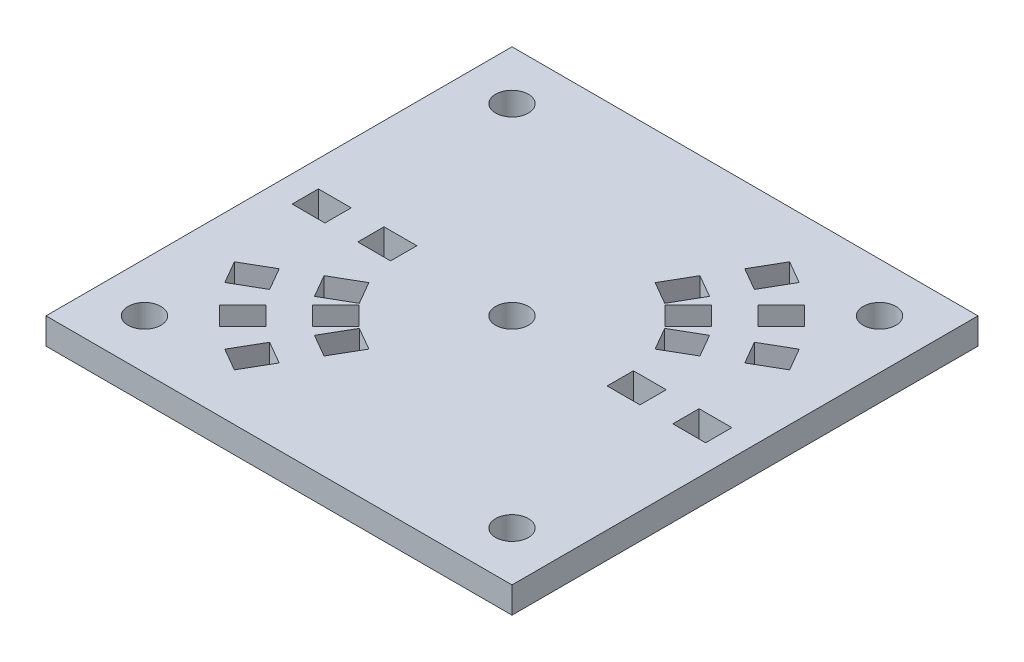
SolidWorks part; units mm, degrees
ref_plane "Front Plane" through (0, 0, 0) normal (0, 0, 1) x (1, 0, 0)
ref_plane "Top Plane" through (0, 0, 0) normal (0, 1, 0) x (1, 0, 0)
ref_plane "Right Plane" through (0, 0, 0) normal (1, 0, 0) x (0, 0, -1)
sketch "Sketch1" plane through (0, 0, 0) normal (0, 1, 0) x (1, 0, 0)
  line L0 (-1.4151, 22.54) -> (-1.4151, -67.6199) construction
  line L1 (-46.495, 22.54) -> (43.6649, 22.54)
  line L2 (-46.495, 22.54) -> (-46.495, -67.6199)
  line L3 (-46.495, -67.6199) -> (43.6649, -67.6199)
  line L4 (43.6649, 22.54) -> (43.6649, -67.6199)
  line L5 (-46.495, -22.54) -> (43.6649, -22.54) construction
  line L6 (-39.3946, -9.7338) -> (-33.261, -11.3773) [skipped]
  line L7 (-41.415, -20) -> (-35.065, -20)
  line L8 (-41.415, -20) -> (-41.415, -25.08)
  line L9 (-41.415, -25.08) -> (-35.065, -25.08)
  line L10 (-35.065, -20) -> (-35.065, -25.08)
  line L11 (-28.715, -20) -> (-22.365, -20)
  line L12 (-28.715, -20) -> (-28.715, -25.08)
  line L13 (-28.715, -25.08) -> (-22.365, -25.08)
  line L14 (-22.365, -20) -> (-22.365, -25.08)
  line L19 (-39.3946, -9.7338) -> (-40.7094, -14.6407) [skipped]
  line L20 (-40.7094, -14.6407) -> (-34.5758, -16.2842) [skipped]
  line L21 (-33.261, -11.3773) -> (-34.5758, -16.2842) [skipped]
  line L22 (-27.1274, -13.0208) -> (-20.9937, -14.6643) [skipped]
  line L23 (-27.1274, -13.0208) -> (-28.4422, -17.9277) [skipped]
  line L24 (-28.4422, -17.9277) -> (-22.3085, -19.5712) [skipped]
  line L25 (-20.9937, -14.6643) -> (-22.3085, -19.5712) [skipped]
  line L30 (-34.786, -0.3403) -> (-29.2868, -3.5153) [skipped]
  line L31 (-34.786, -0.3403) -> (-37.326, -4.7397) [skipped]
  line L32 (-37.326, -4.7397) -> (-31.8268, -7.9147) [skipped]
  line L33 (-29.2868, -3.5153) -> (-31.8268, -7.9147) [skipped]
  line L34 (-23.7875, -6.6903) -> (-18.2882, -9.8653) [skipped]
  line L35 (-23.7875, -6.6903) -> (-26.3275, -11.0897) [skipped]
  line L36 (-26.3275, -11.0897) -> (-20.8282, -14.2647) [skipped]
  line L37 (-18.2882, -9.8653) -> (-20.8282, -14.2647) [skipped]
  line L42 (-27.9032, 7.5403) -> (-23.4131, 3.0502) [skipped]
  line L43 (-27.9032, 7.5403) -> (-31.4953, 3.9482) [skipped]
  line L44 (-31.4953, 3.9482) -> (-27.0052, -0.5419) [skipped]
  line L45 (-23.4131, 3.0502) -> (-27.0052, -0.5419) [skipped]
  line L46 (-18.923, -1.44) -> (-14.4328, -5.9301) [skipped]
  line L47 (-18.923, -1.44) -> (-22.5151, -5.0321) [skipped]
  line L48 (-22.5151, -5.0321) -> (-18.0249, -9.5222) [skipped]
  line L49 (-14.4328, -5.9301) -> (-18.0249, -9.5222) [skipped]
  line L54 (-19.2153, 13.371) -> (-16.0403, 7.8717) [skipped]
  line L55 (-19.2153, 13.371) -> (-23.6147, 10.831) [skipped]
  line L56 (-23.6147, 10.831) -> (-20.4397, 5.3317) [skipped]
  line L57 (-16.0403, 7.8717) -> (-20.4397, 5.3317) [skipped]
  line L58 (-12.8653, 2.3725) -> (-9.6903, -3.1268) [skipped]
  line L59 (-12.8653, 2.3725) -> (-17.2647, -0.1675) [skipped]
  line L60 (-17.2647, -0.1675) -> (-14.0897, -5.6668) [skipped]
  line L61 (-9.6903, -3.1268) -> (-14.0897, -5.6668) [skipped]
  line L66 (-9.3144, 16.7544) -> (-7.6709, 10.6208) [skipped]
  line L67 (-9.3144, 16.7544) -> (-14.2213, 15.4396) [skipped]
  line L68 (-14.2213, 15.4396) -> (-12.5778, 9.306) [skipped]
  line L69 (-7.6709, 10.6208) -> (-12.5778, 9.306) [skipped]
  line L70 (-6.0274, 4.4871) -> (-4.3839, -1.6465) [skipped]
  line L71 (-6.0274, 4.4871) -> (-10.9343, 3.1723) [skipped]
  line L72 (-10.9343, 3.1723) -> (-9.2908, -2.9613) [skipped]
  line L73 (-4.3839, -1.6465) -> (-9.2908, -2.9613) [skipped]
  line L78 (1.1249, 17.46) -> (1.1249, 11.11) [skipped]
  line L79 (1.1249, 17.46) -> (-3.9551, 17.46) [skipped]
  line L80 (-3.9551, 17.46) -> (-3.9551, 11.11) [skipped]
  line L81 (1.1249, 11.11) -> (-3.9551, 11.11) [skipped]
  line L82 (1.1249, 4.76) -> (1.1249, -1.59) [skipped]
  line L83 (1.1249, 4.76) -> (-3.9551, 4.76) [skipped]
  line L84 (-3.9551, 4.76) -> (-3.9551, -1.59) [skipped]
  line L85 (1.1249, -1.59) -> (-3.9551, -1.59) [skipped]
  line L90 (11.3911, 15.4396) -> (9.7476, 9.306) [skipped]
  line L91 (11.3911, 15.4396) -> (6.4842, 16.7544) [skipped]
  line L92 (6.4842, 16.7544) -> (4.8407, 10.6208) [skipped]
  line L93 (9.7476, 9.306) -> (4.8407, 10.6208) [skipped]
  line L94 (8.1041, 3.1723) -> (6.4606, -2.9613) [skipped]
  line L95 (8.1041, 3.1723) -> (3.1972, 4.4871) [skipped]
  line L96 (3.1972, 4.4871) -> (1.5537, -1.6465) [skipped]
  line L97 (6.4606, -2.9613) -> (1.5537, -1.6465) [skipped]
  line L102 (20.7846, 10.831) -> (17.6096, 5.3317)
  line L103 (20.7846, 10.831) -> (16.3852, 13.371)
  line L104 (16.3852, 13.371) -> (13.2102, 7.8717)
  line L105 (17.6096, 5.3317) -> (13.2102, 7.8717)
  line L106 (14.4346, -0.1675) -> (11.2596, -5.6668)
  line L107 (14.4346, -0.1675) -> (10.0352, 2.3725)
  line L108 (10.0352, 2.3725) -> (6.8602, -3.1268)
  line L109 (11.2596, -5.6668) -> (6.8602, -3.1268)
  line L114 (28.6652, 3.9482) -> (24.1751, -0.5419)
  line L115 (28.6652, 3.9482) -> (25.0731, 7.5403)
  line L116 (25.0731, 7.5403) -> (20.583, 3.0502)
  line L117 (24.1751, -0.5419) -> (20.583, 3.0502)
  line L118 (19.6849, -5.0321) -> (15.1948, -9.5222)
  line L119 (19.6849, -5.0321) -> (16.0928, -1.44)
  line L120 (16.0928, -1.44) -> (11.6027, -5.9301)
  line L121 (15.1948, -9.5222) -> (11.6027, -5.9301)
  line L126 (34.4959, -4.7397) -> (28.9966, -7.9147)
  line L127 (34.4959, -4.7397) -> (31.9559, -0.3403)
  line L128 (31.9559, -0.3403) -> (26.4566, -3.5153)
  line L129 (28.9966, -7.9147) -> (26.4566, -3.5153)
  line L130 (23.4974, -11.0897) -> (17.9981, -14.2647)
  line L131 (23.4974, -11.0897) -> (20.9574, -6.6903)
  line L132 (20.9574, -6.6903) -> (15.4581, -9.8653)
  line L133 (17.9981, -14.2647) -> (15.4581, -9.8653)
  line L138 (37.8793, -14.6407) -> (31.7457, -16.2842) [skipped]
  line L139 (37.8793, -14.6407) -> (36.5645, -9.7338) [skipped]
  line L140 (36.5645, -9.7338) -> (30.4309, -11.3773) [skipped]
  line L141 (31.7457, -16.2842) -> (30.4309, -11.3773) [skipped]
  line L142 (25.612, -17.9277) -> (19.4784, -19.5712) [skipped]
  line L143 (25.612, -17.9277) -> (24.2972, -13.0208) [skipped]
  line L144 (24.2972, -13.0208) -> (18.1636, -14.6643) [skipped]
  line L145 (19.4784, -19.5712) -> (18.1636, -14.6643) [skipped]
  line L150 (38.5849, -25.08) -> (32.2349, -25.08)
  line L151 (38.5849, -25.08) -> (38.5849, -20)
  line L152 (38.5849, -20) -> (32.2349, -20)
  line L153 (32.2349, -25.08) -> (32.2349, -20)
  line L154 (25.8849, -25.08) -> (19.5349, -25.08)
  line L155 (25.8849, -25.08) -> (25.8849, -20)
  line L156 (25.8849, -20) -> (19.5349, -20)
  line L157 (19.5349, -25.08) -> (19.5349, -20)
  line L162 (36.5645, -35.3462) -> (30.4309, -33.7027) [skipped]
  line L163 (36.5645, -35.3462) -> (37.8793, -30.4392) [skipped]
  line L164 (37.8793, -30.4392) -> (31.7457, -28.7957) [skipped]
  line L165 (30.4309, -33.7027) -> (31.7457, -28.7957) [skipped]
  line L166 (24.2972, -32.0592) -> (18.1636, -30.4156) [skipped]
  line L167 (24.2972, -32.0592) -> (25.612, -27.1522) [skipped]
  line L168 (25.612, -27.1522) -> (19.4784, -25.5087) [skipped]
  line L169 (18.1636, -30.4156) -> (19.4784, -25.5087) [skipped]
  line L174 (31.9559, -44.7396) -> (26.4566, -41.5646) [skipped]
  line L175 (31.9559, -44.7396) -> (34.4959, -40.3402) [skipped]
  line L176 (34.4959, -40.3402) -> (28.9966, -37.1652) [skipped]
  line L177 (26.4566, -41.5646) -> (28.9966, -37.1652) [skipped]
  line L178 (20.9574, -38.3896) -> (15.4581, -35.2146) [skipped]
  line L179 (20.9574, -38.3896) -> (23.4974, -33.9902) [skipped]
  line L180 (23.4974, -33.9902) -> (17.9981, -30.8152) [skipped]
  line L181 (15.4581, -35.2146) -> (17.9981, -30.8152) [skipped]
  line L186 (25.0731, -52.6202) -> (20.583, -48.1301) [skipped]
  line L187 (25.0731, -52.6202) -> (28.6652, -49.0281) [skipped]
  line L188 (28.6652, -49.0281) -> (24.1751, -44.538) [skipped]
  line L189 (20.583, -48.1301) -> (24.1751, -44.538) [skipped]
  line L190 (16.0928, -43.64) -> (11.6027, -39.1498) [skipped]
  line L191 (16.0928, -43.64) -> (19.6849, -40.0479) [skipped]
  line L192 (19.6849, -40.0479) -> (15.1948, -35.5577) [skipped]
  line L193 (11.6027, -39.1498) -> (15.1948, -35.5577) [skipped]
  line L198 (16.3852, -58.4509) -> (13.2102, -52.9516) [skipped]
  line L199 (16.3852, -58.4509) -> (20.7846, -55.9109) [skipped]
  line L200 (20.7846, -55.9109) -> (17.6096, -50.4116) [skipped]
  line L201 (13.2102, -52.9516) -> (17.6096, -50.4116) [skipped]
  line L202 (10.0352, -47.4524) -> (6.8602, -41.9531) [skipped]
  line L203 (10.0352, -47.4524) -> (14.4346, -44.9124) [skipped]
  line L204 (14.4346, -44.9124) -> (11.2596, -39.4131) [skipped]
  line L205 (6.8602, -41.9531) -> (11.2596, -39.4131) [skipped]
  line L210 (6.4842, -61.8343) -> (4.8407, -55.7007) [skipped]
  line L211 (6.4842, -61.8343) -> (11.3911, -60.5195) [skipped]
  line L212 (11.3911, -60.5195) -> (9.7476, -54.3859) [skipped]
  line L213 (4.8407, -55.7007) -> (9.7476, -54.3859) [skipped]
  line L214 (3.1972, -49.5671) -> (1.5537, -43.4334) [skipped]
  line L215 (3.1972, -49.5671) -> (8.1041, -48.2523) [skipped]
  line L216 (8.1041, -48.2523) -> (6.4606, -42.1186) [skipped]
  line L217 (1.5537, -43.4334) -> (6.4606, -42.1186) [skipped]
  line L222 (-3.9551, -62.5399) -> (-3.9551, -56.1899) [skipped]
  line L223 (-3.9551, -62.5399) -> (1.1249, -62.5399) [skipped]
  line L224 (1.1249, -62.5399) -> (1.1249, -56.1899) [skipped]
  line L225 (-3.9551, -56.1899) -> (1.1249, -56.1899) [skipped]
  line L226 (-3.9551, -49.8399) -> (-3.9551, -43.4899) [skipped]
  line L227 (-3.9551, -49.8399) -> (1.1249, -49.8399) [skipped]
  line L228 (1.1249, -49.8399) -> (1.1249, -43.4899) [skipped]
  line L229 (-3.9551, -43.4899) -> (1.1249, -43.4899) [skipped]
  line L234 (-14.2213, -60.5195) -> (-12.5778, -54.3859) [skipped]
  line L235 (-14.2213, -60.5195) -> (-9.3144, -61.8343) [skipped]
  line L236 (-9.3144, -61.8343) -> (-7.6709, -55.7007) [skipped]
  line L237 (-12.5778, -54.3859) -> (-7.6709, -55.7007) [skipped]
  line L238 (-10.9343, -48.2523) -> (-9.2908, -42.1186) [skipped]
  line L239 (-10.9343, -48.2523) -> (-6.0274, -49.5671) [skipped]
  line L240 (-6.0274, -49.5671) -> (-4.3839, -43.4334) [skipped]
  line L241 (-9.2908, -42.1186) -> (-4.3839, -43.4334) [skipped]
  line L246 (-23.6147, -55.9109) -> (-20.4397, -50.4116)
  line L247 (-23.6147, -55.9109) -> (-19.2153, -58.4509)
  line L248 (-19.2153, -58.4509) -> (-16.0403, -52.9516)
  line L249 (-20.4397, -50.4116) -> (-16.0403, -52.9516)
  line L250 (-17.2647, -44.9124) -> (-14.0897, -39.4131)
  line L251 (-17.2647, -44.9124) -> (-12.8653, -47.4524)
  line L252 (-12.8653, -47.4524) -> (-9.6903, -41.9531)
  line L253 (-14.0897, -39.4131) -> (-9.6903, -41.9531)
  line L258 (-31.4953, -49.0281) -> (-27.0052, -44.538)
  line L259 (-31.4953, -49.0281) -> (-27.9032, -52.6202)
  line L260 (-27.9032, -52.6202) -> (-23.4131, -48.1301)
  line L261 (-27.0052, -44.538) -> (-23.4131, -48.1301)
  line L262 (-22.5151, -40.0479) -> (-18.0249, -35.5577)
  line L263 (-22.5151, -40.0479) -> (-18.923, -43.64)
  line L264 (-18.923, -43.64) -> (-14.4328, -39.1498)
  line L265 (-18.0249, -35.5577) -> (-14.4328, -39.1498)
  line L270 (-37.326, -40.3402) -> (-31.8268, -37.1652)
  line L271 (-37.326, -40.3402) -> (-34.786, -44.7396)
  line L272 (-34.786, -44.7396) -> (-29.2868, -41.5646)
  line L273 (-31.8268, -37.1652) -> (-29.2868, -41.5646)
  line L274 (-26.3275, -33.9902) -> (-20.8282, -30.8152)
  line L275 (-26.3275, -33.9902) -> (-23.7875, -38.3896)
  line L276 (-23.7875, -38.3896) -> (-18.2882, -35.2146)
  line L277 (-20.8282, -30.8152) -> (-18.2882, -35.2146)
  line L282 (-40.7094, -30.4392) -> (-34.5758, -28.7957) [skipped]
  line L283 (-40.7094, -30.4392) -> (-39.3946, -35.3462) [skipped]
  line L284 (-39.3946, -35.3462) -> (-33.261, -33.7027) [skipped]
  line L285 (-34.5758, -28.7957) -> (-33.261, -33.7027) [skipped]
  line L286 (-28.4422, -27.1522) -> (-22.3085, -25.5087) [skipped]
  line L287 (-28.4422, -27.1522) -> (-27.1274, -32.0592) [skipped]
  line L288 (-27.1274, -32.0592) -> (-20.9937, -30.4156) [skipped]
  line L289 (-22.3085, -25.5087) -> (-20.9937, -30.4156) [skipped]
  point P20 (-1.4151, -22.54)
  point P300 (-1.4151, -22.54)
  dimension "D1" = 90.1598
  dimension "D2" = 90.1598
  dimension "D3" = 6.35
  dimension "D4" = 6.35
  dimension "D5" = 6.35
  dimension "D8" = 5.08
  dimension "D9" = 2.54
  dimension "D10" = 5.08
  dimension "D12" = 5.08
  dimension "D14" = 2.54
  dimension "D15" = 24
extrude "Boss-Extrude1" add sketch "Sketch1" along normal blind 5.08
sketch "Sketch2" plane through (0, 5.08, 0) normal (0, 1, 0) x (1, 0, 0)
  line L0 (43.6649, 22.54) -> (-46.495, 22.54) construction
  line L1 (-46.495, 22.54) -> (-46.495, -67.6199) construction
  line L2 (43.6649, -67.6199) -> (43.6649, 22.54) construction
  line L3 (-46.495, -67.6199) -> (43.6649, -67.6199) construction
  line L4 (-1.4151, 22.54) -> (-1.4151, -67.6199) construction
  line L5 (-46.495, -22.54) -> (43.6649, -22.54) construction
  circle A0 centre (-36.97, 13.015) radius 3.175
  circle A1 centre (-36.97, -58.0949) radius 3.175
  circle A2 centre (34.1399, -58.0949) radius 3.175
  circle A3 centre (34.1399, 13.015) radius 3.175
  circle A4 centre (-1.4151, -22.54) radius 3.175
  dimension "D1" = 6.35
  dimension "D2" = 6.35
  dimension "D3" = 6.35
  dimension "D4" = 6.35
  dimension "D13" = 6.35
  dimension "D5" = 9.525
  dimension "D6" = 9.525
  dimension "D7" = 9.525
  dimension "D8" = 9.525
  dimension "D9" = 9.525
  dimension "D10" = 9.525
  dimension "D11" = 9.525
  dimension "D12" = 9.525
extrude "Cut-Extrude1" cut sketch "Sketch2" against normal blind 5.08
